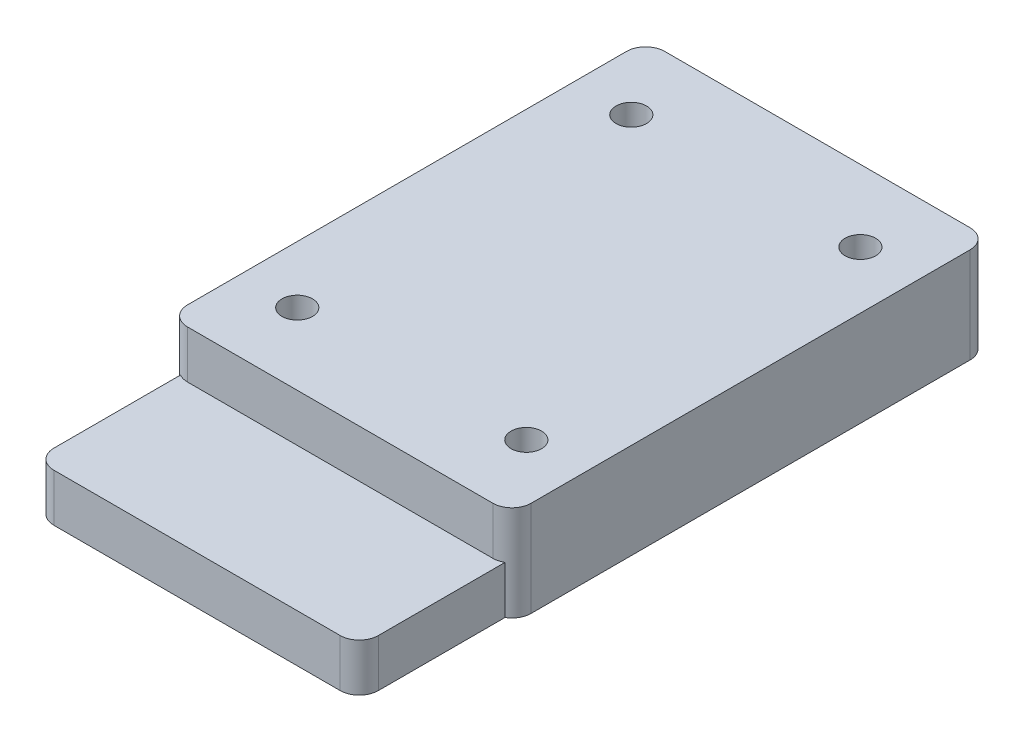
SolidWorks part; units mm, degrees
material "PLA"
ref_plane "前视基准面" through (0, 0, 0) normal (0, 0, 1) x (1, 0, 0)
ref_plane "上视基准面" through (0, 0, 0) normal (0, 1, 0) x (1, 0, 0)
ref_plane "右视基准面" through (0, 0, 0) normal (1, 0, 0) x (0, 0, -1)
sketch "草图1" plane through (0, 0, 0) normal (0, 1, 0) x (1, 0, 0)
  line L5 (-18, 25) -> (18, 25)
  line L6 (-18, 25) -> (-18, -25)
  line L7 (-18, -25) -> (18, -25)
  line L8 (18, 25) -> (18, -25)
  line L9 (0, -25) -> (0, 25) construction
  line L10 (-18, 0) -> (18, 0) construction
  line L11 (-17, -40) -> (17, -40)
  line L12 (-17, -40) -> (-17, -25)
  line L13 (-17, -25) -> (17, -25)
  line L14 (17, -40) -> (17, -25)
  line L15 (0, -25) -> (0, -40) construction
  line L16 (-17, -32.5) -> (17, -32.5) construction
  point P0 (0, 0)
  point P4 (0, -32.5)
  dimension "D1" = 50
  dimension "D2" = 36
  dimension "D3" = 15
  dimension "D4" = 34
extrude "凸台-拉伸1" add sketch "草图1" along normal blind 10 contours L8 L5 L6 L7 | L11 L14 L7 L12 region at (0, 0, 0) region at (0, 0, 32.5)
sketch "草图2" plane through (0, 10, 0) normal (0, 1, 0) x (1, 0, 0)
  line L1 (-12, 17.5) -> (12, 17.5) construction
  line L2 (-12, 17.5) -> (-12, -17.5) construction
  line L3 (-12, -17.5) -> (12, -17.5) construction
  line L4 (12, 17.5) -> (12, -17.5) construction
  line L5 (0, -17.5) -> (0, 17.5) construction
  line L6 (-12, 0) -> (12, 0) construction
  circle A0 centre (12, 17.5) radius 1.6
  circle A1 centre (-12, 17.5) radius 1.6
  circle A2 centre (-12, -17.5) radius 1.6
  circle A3 centre (12, -17.5) radius 1.6
  point P0 (0, 0)
  dimension "D3" = 3.2
  dimension "D1" = 35
  dimension "D2" = 24
extrude "切除-拉伸1" cut sketch "草图2" against normal blind 10
sketch "草图3" plane through (0, 10, 0) normal (0, 1, 0) x (1, 0, 0)
  line L0 (17, -40) -> (17, -25) construction
  line L1 (-17, -25) -> (17, -25)
  line L2 (-17, -25) -> (-17, -40)
  line L3 (-17, -40) -> (17, -40)
  line L4 (17, -25) -> (17, -40)
  line L5 (0, -40) -> (0, -25) construction
  line L6 (-17, -32.5) -> (17, -32.5) construction
  line L7 (-17, -40) -> (-17, -25) construction
  line L8 (-17, -40) -> (17, -40) construction
  line L9 (17, -25) -> (18, -25) construction
  point P0 (0, -32.5)
extrude "切除-拉伸2" cut sketch "草图3" against normal blind 5
fillet "圆角1" radius 2 6 edges at (18, 5, -25) (17, 2.5, 40) (-17, 2.5, 40) (-18, 5, 25) (18, 5, 25) (-18, 5, -25)
